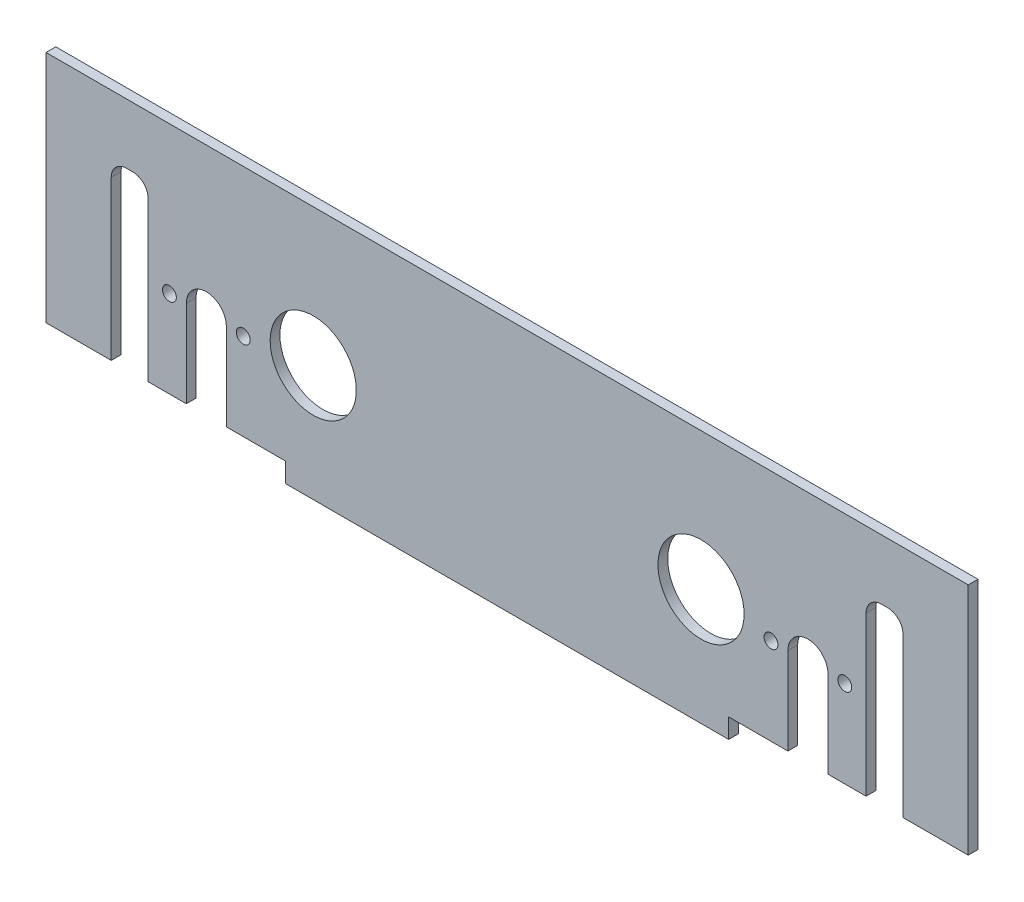
SolidWorks part; units mm, degrees
material "ABS"
ref_plane "X-Y Datum" through (0, 0, 0) normal (0, 0, 1) x (1, 0, 0)
ref_plane "X-Z Datum" through (0, 0, 0) normal (0, 1, 0) x (1, 0, 0)
ref_plane "Y-Z Datum" through (0, 0, 0) normal (1, 0, 0) x (0, 0, -1)
sketch "Sketch1" plane through (0, 0, 0) normal (0, 0, 1) x (1, 0, 0)
  line L1 (-149.85, 38.0375) -> (149.85, 38.0375)
  line L2 (-149.85, 38.0375) -> (-149.85, -38.0375)
  line L3 (-149.85, -38.0375) -> (149.85, -38.0375)
  line L4 (149.85, 38.0375) -> (149.85, -38.0375)
  line L5 (-149.85, 38.0375) -> (149.85, -38.0375) construction
  line L6 (-149.85, -38.0375) -> (149.85, 38.0375) construction
  point P0 (0, 0)
  dimension "D1" = 76.075
  dimension "D2" = 299.7
extrude "Boss-Extrude1" add sketch "Sketch1" along normal blind 3.175
sketch "Sketch3" plane through (0, 0, 0) normal (0, 0, -1) x (-1, 0, 0)
  line L3 (149.85, -38.0375) -> (-149.85, -38.0375) construction
  line L4 (149.85, -38.0375) -> (-149.85, -38.0375)
  line L5 (-104.25, -9.7625) -> (-104.25, -38.0375)
  line L6 (-91.25, -9.7625) -> (-91.25, -38.0375)
  line L7 (104.25, -9.7625) -> (104.25, -38.0375)
  line L8 (91.25, -9.7625) -> (91.25, -38.0375)
  circle A6 centre (-97.75, -9.7625) radius 6.5
  circle A7 centre (97.75, -9.7625) radius 6.5
  point P0 (97.75, -9.7625)
  point P1 (-97.75, -9.7625)
  point P16 (109.75, -9.7625)
  point P17 (85.75, -9.7625)
  point P18 (-85.75, -9.7625)
  point P19 (-109.75, -9.7625)
  dimension "D1" = 13
sketch "Sketch8" plane through (0, 0, 3.175) normal (0, 0, 1) x (1, 0, 0)
  line L0 (128.65, -27.2824) -> (128.65, -38.0375)
  line L1 (121.65, 18.5125) -> (123.65, 18.5125)
  line L3 (-149.85, -38.0375) -> (149.85, -38.0375) construction
  line L4 (122.65, -32.2824) -> (122.65, 18.5125) construction
  line L5 (121.65, -32.2824) -> (123.65, -32.2824)
  line L6 (116.65, -27.2824) -> (116.65, 13.5125)
  line L8 (128.65, -27.2824) -> (128.65, 13.5125)
  line L9 (116.65, -32.2824) -> (128.65, 18.5125) construction
  line L10 (116.65, 18.5125) -> (128.65, -32.2824) construction
  line L12 (116.65, -27.2824) -> (116.65, -38.0375)
  line L13 (-149.85, -38.0375) -> (149.85, -38.0375)
  line L15 (149.85, -38.0375) -> (149.85, 38.0375) construction
  arc A0 (121.65, -32.2824) -> (116.65, -27.2824) centre (121.65, -27.2824) cw
  arc A1 (123.65, -32.2824) -> (128.65, -27.2824) centre (123.65, -27.2824) ccw
  arc A2 (128.65, 13.5125) -> (123.65, 18.5125) centre (123.65, 13.5125) ccw
  arc A3 (121.65, 18.5125) -> (116.65, 13.5125) centre (121.65, 13.5125) ccw
  point P0 (122.65, -6.885)
  line M25 (-149.85, -38.0375) -> (149.85, -38.0375)
  dimension "D1" = 5
  dimension "D2" = 27.2
  dimension "D3" = 31.1525
  dimension "D4" = 12
extrude "Cut-Extrude4" cut sketch "Sketch8" against normal through all contours L1 A3 L6 A0 L5 A1 L8 A2 | A1 L5 A0 L12 L0 M25 region at (122.65, -6.885, 3.175) region at (122.65, -34.6228, 3.175)
mirror "Mirror3" about plane through (0, 0, 0) normal (1, 0, 0) of "Cut-Extrude4"
extrude "Cut-Extrude5" cut sketch "Sketch3" against normal through all contours A6 | A6 L5 L4 L6 | A7 | A7 L8 L4 L7 region at (97.75, -26.4071, 0) region at (-97.75, -26.4071, 0) region at (-97.75, -9.7625, 0) region at (97.75, -9.7625, 0)
hole_wizard "M4 Clearance Hole1" positions "Sketch11" profile "Sketch10" hole size "M4" standard "ANSI Metric" end condition through all
sketch "Sketch11" plane through (0, 0, 0) normal (0, 0, -1) x (-1, 0, 0)
  point P0 (-85.75, -9.7625)
  point P3 (-109.75, -9.7625)
  point P6 (109.75, -9.7625)
  point P9 (85.75, -9.7625)
sketch "Sketch10" plane through (85.75, -9.7625, 0) normal (1, 0, 0) x (0, 1, 0)
  line L0 (0, 0) -> (0, 3.175)
  line L1 (0, 3.175) -> (2.25, 3.175)
  line L2 (2.25, 3.175) -> (2.25, 0)
  line L5 (2.25, 0) -> (0, 0)
  line L11 (0, -6.35) -> (0, 107.95) construction
  dimension "Thru Hole Dia." = 4.5
  dimension "Thru Hole Depth" = 3.175
sketch "Sketch12" plane through (0, -38.0375, 0) normal (0, -1, 0) x (1, 0, 0)
  line L0 (0, 0) -> (0, 3.175) construction
  line L1 (-91.25, 0) -> (91.25, 0) construction
  line L2 (-91.25, 3.175) -> (91.25, 3.175) construction
  line L4 (-72, 3.175) -> (72, 3.175)
  line L5 (-72, 3.175) -> (-72, 0)
  line L6 (-72, 0) -> (72, 0)
  line L7 (72, 3.175) -> (72, 0)
  line L8 (-72, 3.175) -> (72, 0) construction
  line L9 (-72, 0) -> (72, 3.175) construction
  point P6 (0, 1.5875)
  dimension "D1" = 144
extrude "Boss-Extrude2" add sketch "Sketch12" along normal blind 6.35
sketch "Sketch13" plane through (0, 0, 0) normal (0, 0, -1) x (-1, 0, 0)
  line L0 (65.2939, -6.6447) -> (60.7239, -6.6447) construction
  line L1 (65.2939, -2.7997) -> (65.2939, -10.4897) construction
  line L2 (60.7239, -10.7897) -> (60.7239, -2.4997) construction
  circle A0 centre (63.0089, -6.6447) radius 14
  dimension "D1" = 28
extrude "Cut-Extrude6" cut sketch "Sketch13" against normal through all
mirror "Mirror4" about plane through (0, 0, 0) normal (1, 0, 0) of "Cut-Extrude6"
